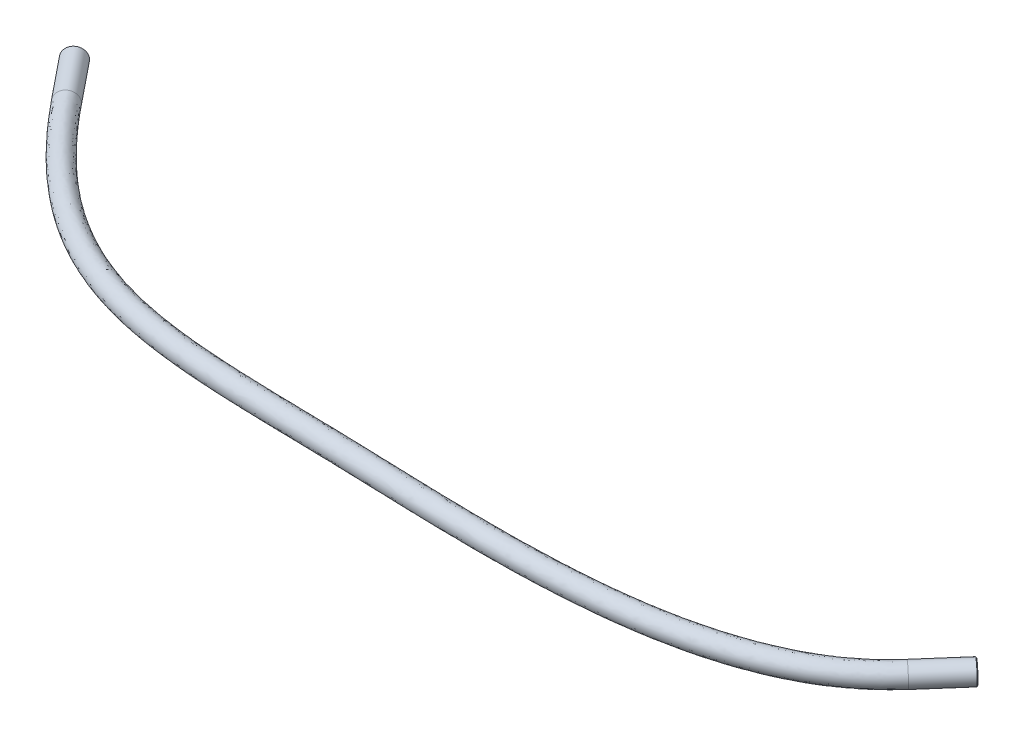
SolidWorks part; units mm, degrees
ref_plane "Front Plane" through (0, 0, 0) normal (0, 0, 1) x (1, 0, 0)
ref_plane "Top Plane" through (0, 0, 0) normal (0, 1, 0) x (1, 0, 0)
ref_plane "Right Plane" through (0, 0, 0) normal (1, 0, 0) x (0, 0, -1)
sketch3d "3DSketch1"
  line L0 (-71.0332, -99.5875, 13.9938) -> (-64.6193, -99.5875, 21.9249)
  line L1 (106.1041, -99.6875, 35.7814) -> (112.1644, -99.6875, 28.8595)
  spline S0 degree 3 poles (-64.6193, -99.5875, 21.9249) (-38.8741, -99.5875, 53.7603) (-0.4815, -99.6375, 49.7137) (88.0798, -99.6875, 56.3683) (106.1041, -99.6875, 35.7814) knots 0 0 0 0 0.53978 1 1 1 1
sketch "Sketch1" plane through (29.6905, 0, -33.9117) normal (-0.6587, 0, 0.7524) x (0.7524, 0, 0.6587)
  circle A0 centre (103.401, -99.6875) radius 1.3
  circle A1 centre (103.401, -99.6875) radius 2
  circle A3 centre (103.401, -99.6875) radius 3.5524 construction
  dimension "D1" = 2.6
  dimension "D2" = 4
sweep "Sweep1" add profiles "Sketch1" path "3DSketch1"
chamfer "Chamfer1" distance 0.127 angle 45 4 edges at (-72.5883, -99.5861, 15.2514) (-72.044, -99.5866, 14.8113) (113.6692, -99.6875, 30.177) (113.1425, -99.6875, 29.7159)
